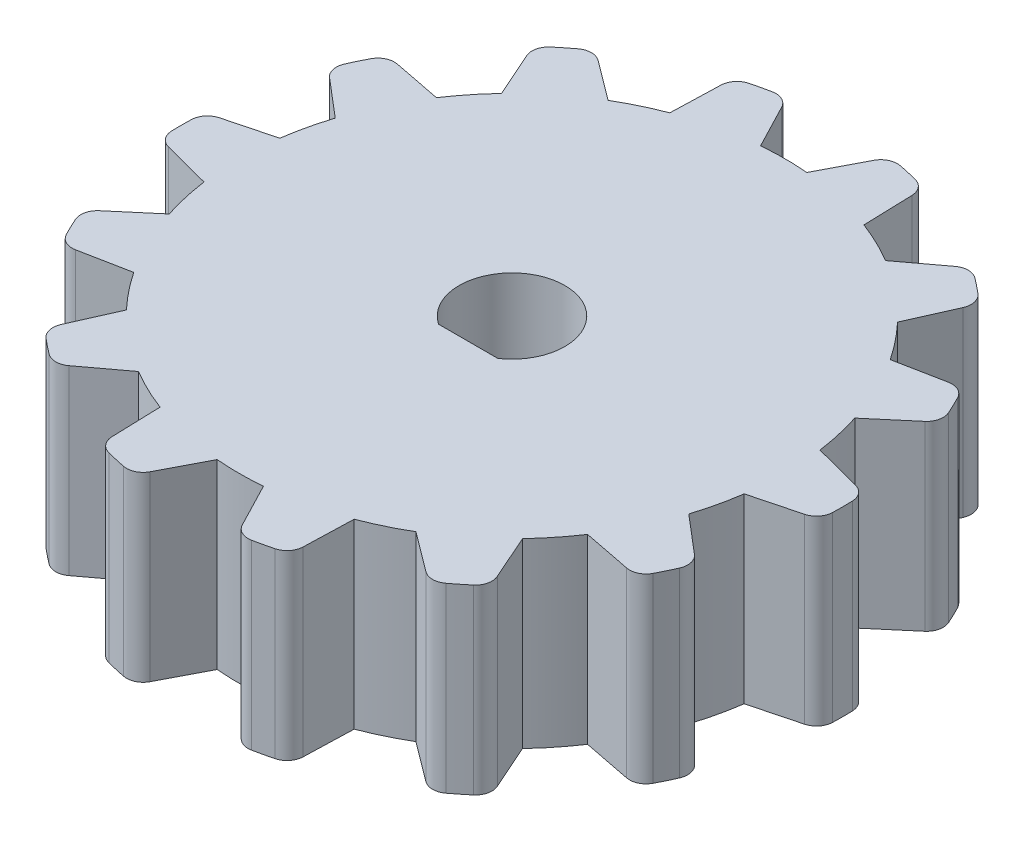
SolidWorks part; units mm, degrees
ref_plane "Front Plane" through (0, 0, 0) normal (0, 0, 1) x (1, 0, 0)
ref_plane "Top Plane" through (0, 0, 0) normal (0, 1, 0) x (1, 0, 0)
ref_plane "Right Plane" through (0, 0, 0) normal (1, 0, 0) x (0, 0, -1)
sketch "Sketch1" plane through (0, 0, 0) normal (0, 1, 0) x (1, 0, 0)
  circle A0 centre (0, 0) radius 20
  dimension "D1" = 40
extrude "Boss-Extrude1" add sketch "Sketch1" along normal blind 11
sketch "Sketch2" plane through (0, 11, 0) normal (0, 1, 0) x (1, 0, 0)
  line L0 (-3.125, 19.7544) -> (-1.3999, 16.4405)
  line L2 (1.3999, 16.4405) -> (3.125, 19.7544)
  circle A0 centre (0, 0) radius 20 construction
  arc A1 (-1.3999, 16.4405) -> (1.3999, 16.4405) centre (0, 0) cw
  arc A2 (3.125, 19.7544) -> (-3.125, 19.7544) centre (0, 0) ccw
  point P6 (0, 16.5)
  dimension "D1" = 16.5
  dimension "D2" = 55
  dimension "D3" = 6.25
extrude "Cut-Extrude1" cut sketch "Sketch2" against normal up to next
fillet "Fillet1" radius 1 2 edges at (3.125, 5.5, -19.7544) (-3.125, 5.5, -19.7544)
pattern_circular "CirPattern1" count 14 over 360 about axis through (0, 11, 0) along (0, -1, 0) of "Cut-Extrude1", "Fillet1"
sketch "Sketch3" plane through (0, 11, 0) normal (0, 1, 0) x (1, 0, 0)
  line L0 (1.7937, -2.65) -> (-1.7937, -2.65)
  arc A0 (1.7937, -2.65) -> (-1.7937, -2.65) centre (0, 0) ccw
  point P1 (0, 3.2)
  dimension "D1" = 3.2
  dimension "D2" = 5.85
extrude "Cut-Extrude2" cut sketch "Sketch3" against normal up to next
